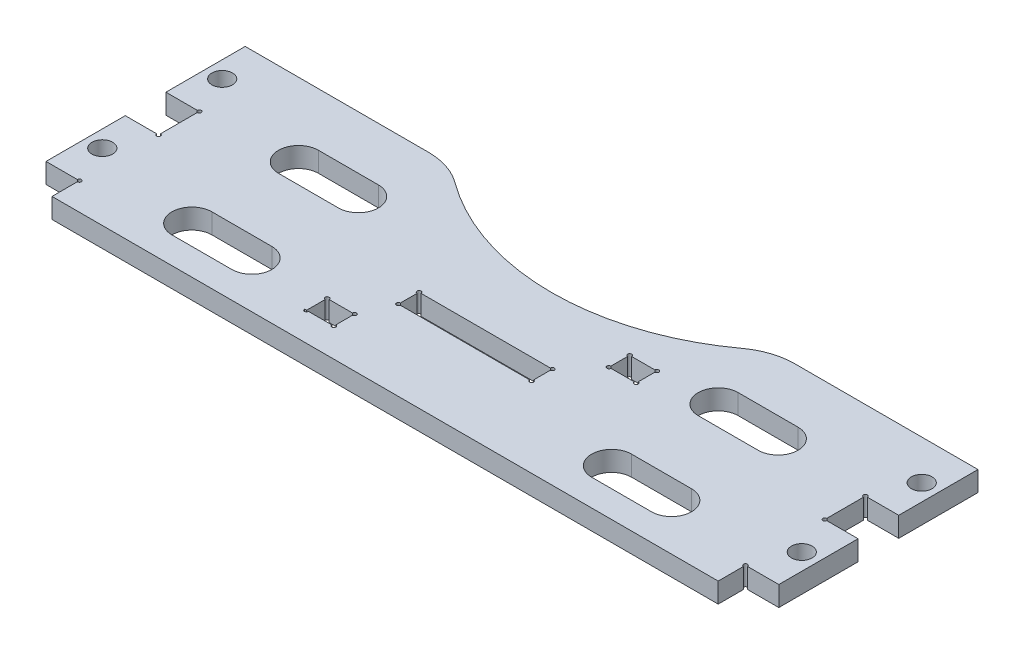
SolidWorks part; units mm, degrees
ref_plane "Front Plane" through (0, 0, 0) normal (0, 0, 1) x (1, 0, 0)
ref_plane "Top Plane" through (0, 0, 0) normal (0, 1, 0) x (1, 0, 0)
ref_plane "Right Plane" through (0, 0, 0) normal (1, 0, 0) x (0, 0, -1)
sketch "Sketch1" plane through (0, 0, 0) normal (0, 1, 0) x (1, 0, 0)
  line L0 (0, 25) -> (0, 0) construction
  line L1 (0, 25) -> (55, 25) construction
  line L2 (55, 34) -> (55, 22.1)
  line L3 (55, 4.1) -> (50, 4.1)
  line L4 (50, 34) -> (55, 34)
  line L5 (27, 10) -> (36, 10)
  line L6 (36, 4) -> (27, 4)
  line L7 (-27, 20) -> (-36, 20)
  line L8 (-36, 26) -> (-27, 26)
  line L9 (-50, 4.1) -> (-50, 0)
  line L10 (-55, 4.1) -> (-50, 4.1)
  line L11 (55, 22.1) -> (50, 22.1)
  line L12 (50, 22.1) -> (50, 16)
  line L13 (50, 16) -> (55, 16)
  line L14 (55, 16) -> (55, 4.1)
  line L15 (50, 4.1) -> (50, 0)
  line L16 (50, 0) -> (-50, 0)
  line L17 (-55, 16) -> (-55, 4.1)
  line L18 (-50, 16) -> (-55, 16)
  line L19 (-50, 22.1) -> (-50, 16)
  line L20 (-55, 22.1) -> (-50, 22.1)
  line L21 (-55, 34) -> (-55, 22.1)
  line L22 (-50, 34) -> (-55, 34)
  line L23 (-50, 15) -> (50, 15) construction
  line L24 (36, 26) -> (27, 26)
  line L25 (27, 20) -> (36, 20)
  line L26 (-36, 4) -> (-27, 4)
  line L27 (-27, 10) -> (-36, 10)
  line L28 (50, 34) -> (24, 34)
  line L29 (-50, 34) -> (-24, 34)
  arc A0 (24, 34) -> (-24, 34) centre (0, 61.5) cw
  arc A1 (36, 10) -> (36, 4) centre (36, 7) cw
  arc A2 (27, 10) -> (27, 4) centre (27, 7) ccw
  arc A3 (-36, 20) -> (-36, 26) centre (-36, 23) cw
  arc A4 (-27, 20) -> (-27, 26) centre (-27, 23) ccw
  arc A5 (27, 20) -> (27, 26) centre (27, 23) cw
  arc A6 (36, 20) -> (36, 26) centre (36, 23) ccw
  arc A7 (-27, 10) -> (-27, 4) centre (-27, 7) cw
  arc A8 (-36, 10) -> (-36, 4) centre (-36, 7) ccw
  point P53 (23.7734, 33.1597)
  dimension "D5" = 9
  dimension "D8" = 7
  dimension "D7" = 27
  dimension "D6" = 3
  dimension "D1" = 5
  dimension "D2" = 4.1
  dimension "D3" = 6.1
  dimension "D4" = 24
  dimension "D9" = 11.9
  dimension "D10" = 11.9
  dimension "D11" = 55
  dimension "D12" = 9
  dimension "D16" = 15
extrude "Boss-Extrude1" add sketch "Sketch1" along normal blind 3
sketch "Sketch2" plane through (0, 3, 0) normal (0, 1, 0) x (1, 0, 0)
  line L1 (-16.1, 7.4) -> (-12, 7.4)
  line L2 (-16.1, 7.4) -> (-16.1, 4.3)
  line L3 (-16.1, 4.3) -> (-12, 4.3)
  line L4 (-12, 7.4) -> (-12, 4.3)
  line L5 (14, 22.7) -> (18.1, 22.7)
  line L6 (14, 22.7) -> (14, 19.6)
  line L7 (14, 19.6) -> (18.1, 19.6)
  line L8 (18.1, 22.7) -> (18.1, 19.6)
  line L9 (-50, 0) -> (50, 0) construction
  dimension "D1" = 12
  dimension "D2" = 4.1
  dimension "D3" = 3.1
  dimension "D4" = 7.4
  dimension "D5" = 14
  dimension "D6" = 19.6
extrude "Cut-Extrude1" cut sketch "Sketch2" against normal blind 10
sketch "Sketch5" plane through (0, 3, 0) normal (0, 1, 0) x (1, 0, 0)
  line L0 (0, 0) -> (0, 15.1) construction
  line L1 (-10, 15.1) -> (10, 15.1)
  line L2 (-10, 15.1) -> (-10, 12)
  line L3 (-10, 12) -> (10, 12)
  line L4 (10, 15.1) -> (10, 12)
  line L6 (52.5, 28.05) -> (52.5, 10.05) construction
  line L7 (55, 22.1) -> (55, 34) construction
  line L9 (55, 10.05) -> (52.5, 10.05) construction
  line L10 (55, 4.1) -> (55, 16) construction
  line L11 (55, 28.05) -> (52.5, 28.05) construction
  circle A0 centre (52.5, 28.05) radius 1.55
  circle A1 centre (52.5, 10.05) radius 1.55
  circle A2 centre (-52.5, 10.05) radius 1.55
  circle A3 centre (-52.5, 28.05) radius 1.55
  dimension "D4" = 3.1
  dimension "D1" = 20
  dimension "D2" = 3.1
  dimension "D3" = 12
  dimension "D5" = 2.5
extrude "Cut-Extrude3" cut sketch "Sketch5" against normal blind 3 contours A0 | A1 | A3 | A2 | L3 L4 L1 L2 region at (52.5, 3, -28.05) region at (52.5, 3, -10.05) region at (-52.5, 3, -10.05) region at (-52.5, 3, -28.05)
sketch "Sketch4" plane through (0, 3, 0) normal (0, 1, 0) x (1, 0, 0)
  line L0 (-55, 4.1) -> (-50, 4.1) construction
  line L1 (-50, 4.1) -> (-50, 0) construction
  line L2 (-50.3, 4.1) -> (-50, 4.1)
  line L3 (-50, 4.1) -> (-50, 3.8)
  line L7 (-55, 22.1) -> (-50, 22.1) construction
  line L8 (-50, 22.1) -> (-50, 16) construction
  line L9 (-50, 16) -> (-55, 16) construction
  line L10 (-50.3, 22.1) -> (-50, 22.1)
  line L11 (-50, 22.1) -> (-50, 21.8)
  line L12 (-50, 16.3) -> (-50, 16)
  line L13 (-50, 16) -> (-50.3, 16)
  line L14 (0, 0) -> (0, 21.5) construction
  line L15 (50, 16) -> (50.3, 16)
  line L16 (50, 16.3) -> (50, 16)
  line L17 (50, 22.1) -> (50, 21.8)
  line L18 (50.3, 22.1) -> (50, 22.1)
  line L21 (50, 4.1) -> (50, 3.8)
  line L22 (50.3, 4.1) -> (50, 4.1)
  line L23 (-12, 7.4) -> (-16.1, 7.4) construction
  line L24 (-12, 4.3) -> (-12, 7.4) construction
  line L25 (-16.1, 7.4) -> (-16.1, 4.3) construction
  line L26 (-16.1, 4.3) -> (-12, 4.3) construction
  line L27 (-16.1, 7.1) -> (-16.1, 7.4)
  line L28 (-16.1, 7.4) -> (-15.8, 7.4)
  line L29 (-12.3, 7.4) -> (-12, 7.4)
  line L30 (-12, 7.4) -> (-12, 7.1)
  line L31 (-12, 4.6) -> (-12, 4.3)
  line L32 (-12, 4.3) -> (-12.3, 4.3)
  line L33 (-12.3, 4.3) -> (-18.2591, 4.3251)
  line L34 (-15.8, 4.3) -> (-16.1, 4.3)
  line L35 (-16.1, 4.3) -> (-16.1, 4.6)
  line L36 (14, 22.4) -> (14, 22.7)
  line L37 (14, 22.7) -> (14.3, 22.7)
  line L38 (17.8, 22.7) -> (18.1, 22.7)
  line L39 (18.1, 22.7) -> (18.1, 22.4)
  line L40 (18.1, 19.9) -> (18.1, 19.6)
  line L41 (18.1, 19.6) -> (17.8, 19.6)
  line L43 (14.3, 19.6) -> (14, 19.6)
  line L44 (14, 19.6) -> (14, 19.9)
  line L45 (-10, 14.8) -> (-10, 15.1)
  line L46 (-10, 15.1) -> (-9.7, 15.1)
  line L47 (9.7, 15.1) -> (10, 15.1)
  line L48 (10, 15.1) -> (10, 14.8)
  line L49 (10, 12.3) -> (10, 12)
  line L50 (10, 12) -> (9.7, 12)
  line L51 (9.7, 12) -> (9.7409, 12.0251)
  line L52 (-9.7, 12) -> (-10, 12)
  line L53 (-10, 12) -> (-10, 12.3)
  arc A0 (-50.3, 4.1) -> (-50, 3.8) centre (-50, 4.1) cw
  arc A2 (-50.3, 22.1) -> (-50, 21.8) centre (-50, 22.1) cw
  arc A3 (-50, 16.3) -> (-50.3, 16) centre (-50, 16) cw
  arc A4 (50, 16.3) -> (50.3, 16) centre (50, 16) ccw
  arc A5 (50.3, 22.1) -> (50, 21.8) centre (50, 22.1) ccw
  arc A7 (50.3, 4.1) -> (50, 3.8) centre (50, 4.1) ccw
  arc A8 (-12.3, 7.4) -> (-12, 7.1) centre (-12, 7.4) cw
  arc A9 (-15.8, 7.4) -> (-16.1, 7.1) centre (-16.1, 7.4) ccw
  arc A10 (-16.1, 4.6) -> (-15.8, 4.3) centre (-16.1, 4.3) ccw
  arc A11 (-12, 4.6) -> (-12.3, 4.3) centre (-12, 4.3) cw
  arc A12 (17.8, 22.7) -> (18.1, 22.4) centre (18.1, 22.7) cw
  arc A13 (14.3, 22.7) -> (14, 22.4) centre (14, 22.7) ccw
  arc A14 (14, 19.9) -> (14.3, 19.6) centre (14, 19.6) ccw
  arc A15 (18.1, 19.9) -> (17.8, 19.6) centre (18.1, 19.6) cw
  arc A16 (9.7, 15.1) -> (10, 14.8) centre (10, 15.1) cw
  arc A17 (-9.7, 15.1) -> (-10, 14.8) centre (-10, 15.1) ccw
  arc A18 (-10, 12.3) -> (-9.7, 12) centre (-10, 12) ccw
  arc A19 (10, 12.3) -> (9.7, 12) centre (10, 12) cw
  line M1 (18.1, 19.6) -> (14, 19.6)
  line M2 (14, 19.6) -> (14, 22.7)
  line M3 (14, 22.7) -> (18.1, 22.7)
  line M4 (18.1, 22.7) -> (18.1, 19.6)
  line M5 (-12, 4.3) -> (-16.1, 4.3)
  line M6 (-16.1, 4.3) -> (-16.1, 7.4)
  line M7 (-16.1, 7.4) -> (-12, 7.4)
  line M8 (-12, 7.4) -> (-12, 4.3)
  line M21 (50, 0) -> (50, 4.1)
  line M24 (55, 16) -> (50, 16)
  line M25 (50, 16) -> (50, 22.1)
  line M26 (50, 22.1) -> (55, 22.1)
  line M33 (-50, 22.1) -> (-50, 16)
  line M34 (-50, 16) -> (-55, 16)
  line M37 (-50, 4.1) -> (-50, 0)
  dimension "D1" = 0.3
  dimension "D2" = 0.3
  dimension "D3" = 0.3
  dimension "D4" = 0.3
extrude "Cut-Extrude2" cut sketch "Sketch4" against normal blind 10 contours A3 M33 M34 | M37 | A9 M7 M6 | A8 M7 M8 | A11 M8 M5 | A10 M6 M5 | A13 M3 M2 | A12 M3 M4 | A14 M2 M1 | A15 M4 M1 | A5 M26 M25 | A4 M25 M24 | M21 | A16 L47 L48 | A19 L49 L50 | A2 L11 L10 | A0 L3 L2 | A7 L21 L22 | A17 L45 L46 | A18 L52 L53 region at (-49.9576, 3, -4.1424) region at (-49.9576, 3, -15.9576) region at (49.9576, 3, -22.1424) region at (49.9576, 3, -15.9576) region at (49.9576, 3, -4.1424) region at (-16.1424, 3, -7.4424) region at (-11.9576, 3, -7.4424) region at (-16.1052, 3, -4.1773) region at (-11.9576, 3, -4.2576) region at (13.9576, 3, -22.7424) region at (13.9576, 3, -19.5576) region at (18.1424, 3, -22.7424) region at (18.1424, 3, -19.5576) region at (10.0424, 3, -15.1424) region at (10.0424, 3, -11.9576)
fillet "Fillet1" radius 10 2 edges at (24, 1.5, -34) (-24, 1.5, -34)
